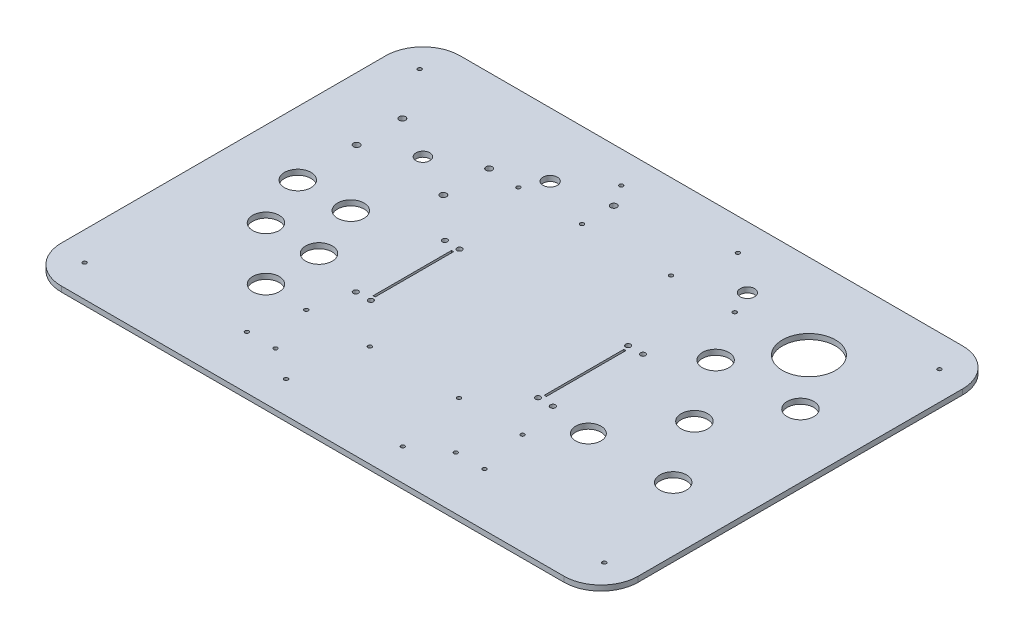
SolidWorks part; units mm, degrees
material "Perspex (TM) GS Acrylic Cast Sheet"
ref_plane "Front Plane" through (0, 0, 0) normal (0, 0, 1) x (1, 0, 0)
ref_plane "Top Plane" through (0, 0, 0) normal (0, 1, 0) x (1, 0, 0)
ref_plane "Right Plane" through (0, 0, 0) normal (1, 0, 0) x (0, 0, -1)
sketch "Sketch1" plane through (0, 0, 0) normal (0, 1, 0) x (1, 0, 0)
  line L1 (0, 0) -> (544, 0)
  line L2 (0, 0) -> (0, 376)
  line L3 (0, 376) -> (544, 376)
  line L4 (544, 0) -> (544, 376)
  dimension "D1" = 544
  dimension "D2" = 376
extrude "Boss-Extrude1" add sketch "Sketch1" along normal blind 5
sketch "Sketch2" plane through (0, 5, 0) normal (0, 1, 0) x (1, 0, 0)
  line L0 (544, 376) -> (0, 376) construction
  line L1 (100, 276) -> (165.8433, 276) construction
  line L2 (100, 276) -> (100, 296.2555) construction
  line L3 (0, 376) -> (0, 0) construction
  circle A0 centre (100, 276) radius 6.5
  circle A2 centre (140.91, 297.59) radius 3
  circle A3 centre (140.91, 254.41) radius 3
  circle A4 centre (59.09, 254.41) radius 3
  circle A5 centre (59.09, 297.59) radius 3
  dimension "D1" = 13
  dimension "D2" = 100
  dimension "D5" = 6
  dimension "D3" = 40.91
  dimension "D4" = 21.59
  dimension "D6" = 100
extrude "1 Joyystick" cut sketch "Sketch2" against normal through all
sketch "Sketch3" plane through (0, 5, 0) normal (0, 1, 0) x (1, 0, 0)
  line L0 (0, 376) -> (0, 0) construction
  line L2 (512, 378) -> (32, 378) construction
  circle A0 centre (60, 198) radius 12.5
  circle A1 centre (110, 198) radius 12.5
  circle A2 centre (80, 148) radius 12.5
  circle A3 centre (130, 148) radius 12.5
  circle A4 centre (130, 98) radius 12.5
  dimension "D1" = 25
  dimension "D2" = 25
  dimension "D3" = 25
  dimension "D4" = 25
  dimension "D5" = 25
  dimension "D11" = 180
  dimension "D6" = 60
  dimension "D7" = 50
  dimension "D8" = 50
  dimension "D9" = 50
  dimension "D10" = 50
  dimension "D12" = 20
extrude "1 Buttons" cut sketch "Sketch3" against normal through all
sketch "Sketch4" plane through (0, 5, 0) normal (0, 1, 0) x (1, 0, 0)
  line L0 (544, 376) -> (0, 376) construction
  line L1 (0, 376) -> (0, 0) construction
  circle A0 centre (180, 316) radius 6.75
  dimension "D1" = 13.5
  dimension "D2" = 60
  dimension "D3" = 180
extrude "1 Rocket Switch" cut sketch "Sketch4" against normal through all
sketch "Sketch5" plane through (0, 5, 0) normal (0, 1, 0) x (1, 0, 0)
  line L0 (192, 176) -> (210.2533, 176) construction
  line L1 (190, 213) -> (192, 213)
  line L2 (190, 213) -> (190, 139)
  line L3 (190, 139) -> (192, 139)
  line L4 (192, 213) -> (192, 139)
  line L5 (190, 176) -> (192, 176) construction
  line L7 (544, 376) -> (0, 376) construction
  line L8 (185.3835, 194.2678) -> (184.0453, 100.019) construction
  line L9 (0, 376) -> (0, 0) construction
  circle A0 centre (178.7197, 218) radius 2.4
  circle A1 centre (192.7183, 217.8012) radius 2.4
  circle A2 centre (192.7183, 134.1988) radius 2.4
  circle A3 centre (178.7197, 134) radius 2.4
  point P7 (191, 213)
  dimension "D5" = 4.8
  dimension "D1" = 2
  dimension "D2" = 74
  dimension "D3" = 5.35
  dimension "D4" = 190
  dimension "D6" = 7
  dimension "D7" = 200
  dimension "D8" = 5
  dimension "D9" = 4.8012
extrude "1 Potentiometer" cut sketch "Sketch5" against normal through all
fillet "Fillet1" radius 35 4 edges at (0, 2.5, 0) (544, 2.5, 0) (544, 2.5, -376) (0, 2.5, -376)
sketch "Sketch6" plane through (0, 5, 0) normal (0, 1, 0) x (1, 0, 0)
  line L0 (544, 35) -> (544, 341) construction
  line L2 (544, 188) -> (0, 188) construction
  line L3 (0, 341) -> (0, 35) construction
  circle A0 centre (484, 248) radius 12.5
  circle A1 centre (404, 248) radius 12.5
  circle A2 centre (484, 128) radius 12.5
  circle A3 centre (404, 128) radius 12
  circle A4 centre (444, 188) radius 12.5
  dimension "D1" = 25
  dimension "D2" = 25
  dimension "D3" = 24
  dimension "D4" = 25
  dimension "D5" = 25
  dimension "D6" = 80
  dimension "D7" = 60
  dimension "D8" = 80
  dimension "D9" = 120
  dimension "D10" = 60
  dimension "D11" = 60
  dimension "D12" = 40
extrude "2 Buttons" cut sketch "Sketch6" against normal through all
sketch "Sketch8" plane through (0, 5, 0) normal (0, 1, 0) x (1, 0, 0)
  line L0 (353, 213.5) -> (353, 138.5) construction
  line L1 (354, 213.5) -> (352, 213.5)
  line L2 (354, 213.5) -> (354, 138.5)
  line L3 (354, 138.5) -> (352, 138.5)
  line L4 (352, 213.5) -> (352, 138.5)
  line L5 (358, 205.9826) -> (358, 86.9169) construction
  line L6 (354, 176) -> (327.2352, 176) construction
  line L8 (544, 35) -> (544, 341) construction
  line L9 (509, 376) -> (35, 376) construction
  circle A0 centre (365, 218.5) radius 2.4
  circle A1 centre (365, 133.5) radius 2.4
  circle A2 centre (351, 133.5) radius 2.4
  circle A3 centre (351, 218.5) radius 2.4
  point P22 (353, 176)
  dimension "D2" = 4.8
  dimension "D3" = 42.5
  dimension "D1" = 5
  dimension "D4" = 1
  dimension "D5" = 2
  dimension "D6" = 190
  dimension "D7" = 200
  dimension "D8" = 7
sketch "Sketch9" plane through (0, 5, 0) normal (0, 1, 0) x (1, 0, 0)
  line L0 (544, 35) -> (544, 341) construction
  line L1 (509, 376) -> (35, 376) construction
  circle A0 centre (444, 296) radius 25
  dimension "D1" = 50
  dimension "D2" = 100
  dimension "D3" = 80
extrude "2 speaker" cut sketch "Sketch9" against normal through all
sketch "Sketch10" plane through (0, 5, 0) normal (0, 1, 0) x (1, 0, 0)
  line L1 (544, 35) -> (544, 341) construction
  line L2 (512, 378) -> (32, 378) construction
  circle A0 centre (364, 318) radius 6.75
  dimension "D1" = 13.5
  dimension "D2" = 60
  dimension "D3" = 180
extrude "2 Rocket Switch" cut sketch "Sketch10" against normal through all
extrude "2 Potentiometer" cut sketch "Sketch8" against normal through all
sketch "Sketch11" plane through (0, 5, 0) normal (0, 1, 0) x (1, 0, 0)
  line L0 (314, 96) -> (314, 294.2) construction
  line L1 (374, 96) -> (374, 296) construction
  line L2 (365.4787, 96) -> (281.3845, 96) construction
  line L3 (356.6021, 296) -> (314, 296) construction
  line L4 (544, 35) -> (544, 341) construction
  line L5 (509, 376) -> (35, 376) construction
  circle A0 centre (374, 96) radius 1.8
  circle A1 centre (314, 96) radius 1.8
  circle A2 centre (314, 296) radius 1.8
  circle A3 centre (374, 296) radius 1.8
  dimension "D1" = 200
  dimension "D3" = 3.6
  dimension "D4" = 3.6
  dimension "D5" = 3.6
  dimension "D6" = 3.6
  dimension "D2" = 60
  dimension "D7" = 170
  dimension "D8" = 80
extrude "2 PCB1" cut sketch "Sketch11" against normal through all
sketch "Sketch12" plane through (0, 5, 0) normal (0, 1, 0) x (1, 0, 0)
  line L0 (159.4963, 96) -> (271.8437, 96) construction
  line L1 (244.3419, 296) -> (170, 296) construction
  line L2 (230, 96) -> (230, 296) construction
  line L3 (170, 30.2464) -> (170, 266.6202) construction
  line L5 (509, 376) -> (35, 376) construction
  line L6 (0, 341) -> (0, 35) construction
  circle A0 centre (230, 96) radius 1.8
  circle A1 centre (170, 96) radius 1.8
  circle A2 centre (230, 296) radius 1.8
  circle A3 centre (170, 296) radius 1.8
  dimension "D3" = 3.6
  dimension "D4" = 3.6
  dimension "D7" = 3.6
  dimension "D8" = 3.6
  dimension "D1" = 200
  dimension "D2" = 60
  dimension "D5" = 170
  dimension "D6" = 80
extrude "1 PCB2" cut sketch "Sketch12" against normal through all
sketch "Sketch13" plane through (0, 5, 0) normal (0, 1, 0) x (1, 0, 0)
  line L1 (544, 35) -> (544, 341) construction
  line L2 (35, 0) -> (509, 0) construction
  circle A0 centre (384, 50) radius 1.8
  circle A1 centre (357, 50) radius 1.8
  dimension "D1" = 3.6
  dimension "D2" = 3.6
  dimension "D3" = 27
  dimension "D4" = 50
  dimension "D5" = 160
extrude "2 USB Connector" cut sketch "Sketch13" against normal through all
sketch "Sketch14" plane through (0, 5, 0) normal (0, 1, 0) x (1, 0, 0)
  line L1 (0, 341) -> (0, 35) construction
  line L2 (35, 0) -> (509, 0) construction
  circle A0 centre (187, 50) radius 1.8
  circle A1 centre (160, 50) radius 1.8
  dimension "D1" = 3.6
  dimension "D2" = 3.6
  dimension "D4" = 50
  dimension "D3" = 27
  dimension "D5" = 160
extrude "1 USB Connector" cut sketch "Sketch14" against normal through all
sketch "Sketch15" plane through (0, 5, 0) normal (0, 1, 0) x (1, 0, 0)
  line L0 (509, 376) -> (35, 376) construction
  line L1 (0, 341) -> (0, 35) construction
  circle A0 centre (230, 326) radius 3
  dimension "D1" = 6
  dimension "D2" = 50
  dimension "D3" = 230
extrude "Power" cut sketch "Sketch15" against normal through all
sketch "Sketch16" plane through (0, 5, 0) normal (0, 1, 0) x (1, 0, 0)
  line L0 (544, 35) -> (544, 341) construction
  line L1 (35, 0) -> (509, 0) construction
  line L2 (272, 0) -> (272, 376) construction
  line L3 (509, 376) -> (35, 376) construction
  circle A0 centre (517, 30) radius 1.8
  circle A1 centre (327, 30) radius 1.8
  circle A2 centre (517, 346) radius 1.8
  circle A3 centre (327, 346) radius 1.8
  circle A4 centre (217, 346) radius 1.8
  circle A5 centre (27, 346) radius 1.8
  circle A6 centre (217, 30) radius 1.8
  circle A7 centre (27, 30) radius 1.8
  dimension "D1" = 27
  dimension "D3" = 3.6
  dimension "D5" = 3.6
  dimension "D8" = 3.6
  dimension "D9" = 3.6
  dimension "D2" = 30
  dimension "D4" = 190
  dimension "D6" = 316
  dimension "D7" = 316
extrude "LED fixings" cut sketch "Sketch16" against normal through all
